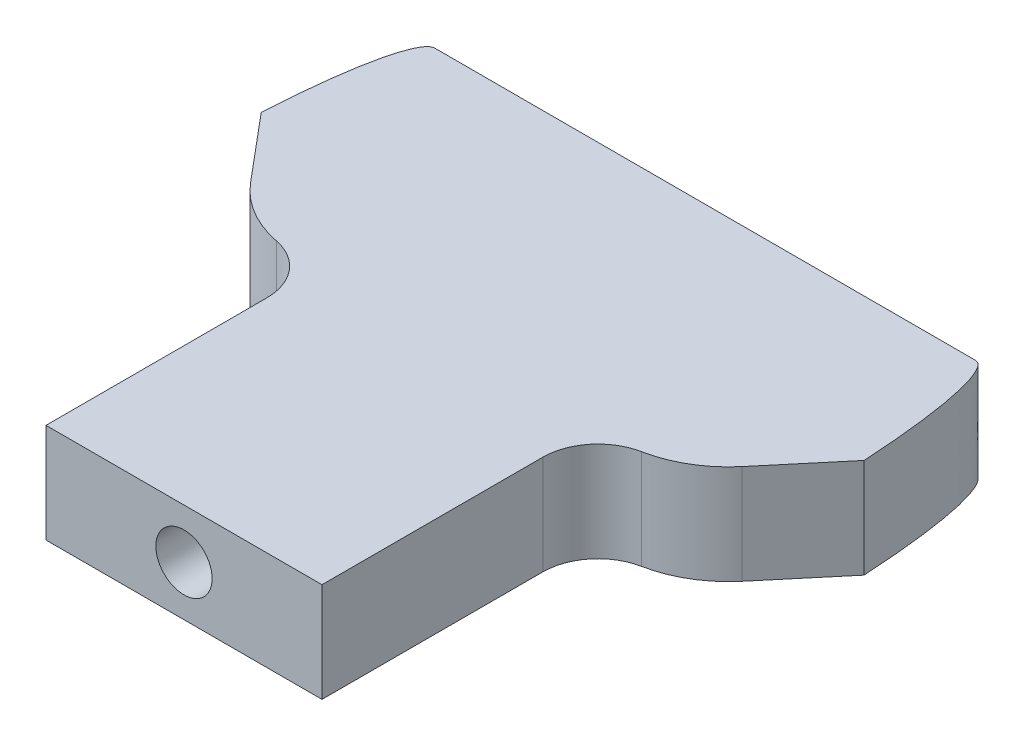
SolidWorks part; units mm, degrees
material "7050-T7651"
ref_plane "Front Plane" through (0, 0, 0) normal (0, 0, 1) x (1, 0, 0)
ref_plane "Top Plane" through (0, 0, 0) normal (0, 1, 0) x (1, 0, 0)
ref_plane "Right Plane" through (0, 0, 0) normal (1, 0, 0) x (0, 0, -1)
sketch "Sketch2" plane through (0, 0, 0) normal (0, 0, 1) x (1, 0, 0)
  line L1 (-27.5, -4.5) -> (27.5, -4.5)
  line L2 (-27.5, -4.5) -> (-27.5, 4.5)
  line L3 (-27.5, 4.5) -> (27.5, 4.5)
  line L4 (27.5, -4.5) -> (27.5, 4.5)
  circle A0 centre (0, 0) radius 2.55
  point P7 (0, 4.5)
  point P8 (-27.5, 0)
  dimension "D1" = 5.1
  dimension "D2" = 4.5
  dimension "D3" = 55
extrude "Boss-Extrude1" add sketch "Sketch2" against normal blind 12.2
cosmetic thread "Cosmetic Thread1" parameters "D1"=10, "D2"=6
sketch "Sketch3" plane through (0, 0, -12.2) normal (0, 0, -1) x (-1, 0, 0)
  line L1 (-27.5, -4.5) -> (27.5, -4.5)
  line L2 (-27.5, -4.5) -> (-27.5, 4.5)
  line L3 (-27.5, 4.5) -> (27.5, 4.5)
  line L4 (27.5, -4.5) -> (27.5, 4.5)
extrude "Boss-Extrude2" add sketch "Sketch3" along normal blind 35
sketch "Sketch4" plane through (0, 0, -47.2) normal (0, 0, -1) x (-1, 0, 0)
  line L0 (27.5, -4.5) -> (27.5, 4.5) construction
  line L1 (-27.5, -4.5) -> (27.5, -4.5)
  line L2 (-27.5, -4.5) -> (-27.5, -0.5)
  line L3 (-27.5, -0.5) -> (27.5, -0.5)
  line L4 (27.5, -4.5) -> (27.5, -0.5)
  dimension "D1" = 4
sketch "Sketch5" plane through (0, -4.5, 0) normal (0, -1, 0) x (1, 0, 0)
  line L0 (0, 0) -> (0, -23.819) construction
  line L1 (27.5, 0) -> (12.5, 0)
  line L2 (27.5, 0) -> (27.5, -25)
  line L3 (27.5, -25) -> (17.5, -25)
  line L4 (12.5, 0) -> (12.5, -20)
  line L5 (-12.5, 0) -> (-12.5, -20)
  line L6 (-27.5, -25) -> (-17.5, -25)
  line L7 (-27.5, 0) -> (-27.5, -25)
  line L8 (-27.5, 0) -> (-12.5, 0)
  arc A0 (17.5, -25) -> (12.5, -20) centre (17.5, -20) cw
  arc A1 (-17.5, -25) -> (-12.5, -20) centre (-17.5, -20) ccw
  point P10 (12.5, -25)
  dimension "D3" = 5
  dimension "D1" = 15
  dimension "D2" = 25
extrude "Cut-Extrude1" cut sketch "Sketch5" against normal up to next
chamfer "Chamfer1" distance 8 angle 50 2 edges at (-27.5, 0, -25) (27.5, 0, -25) first distance on face at (-22.5, 0, -25) first distance on face at (22.5, 0, -25)
fillet "Fillet1" radius 20 2 edges at (-27.5, 0, -47.2) (27.5, 0, -47.2) second distance 3 first distance on face at (-27.5, 0, -40.867) first distance on face at (27.5, 0, -40.867)
fillet "Fillet2" radius 10 2 edges at (19.5, 0, -25) (-19.5, 0, -25)
